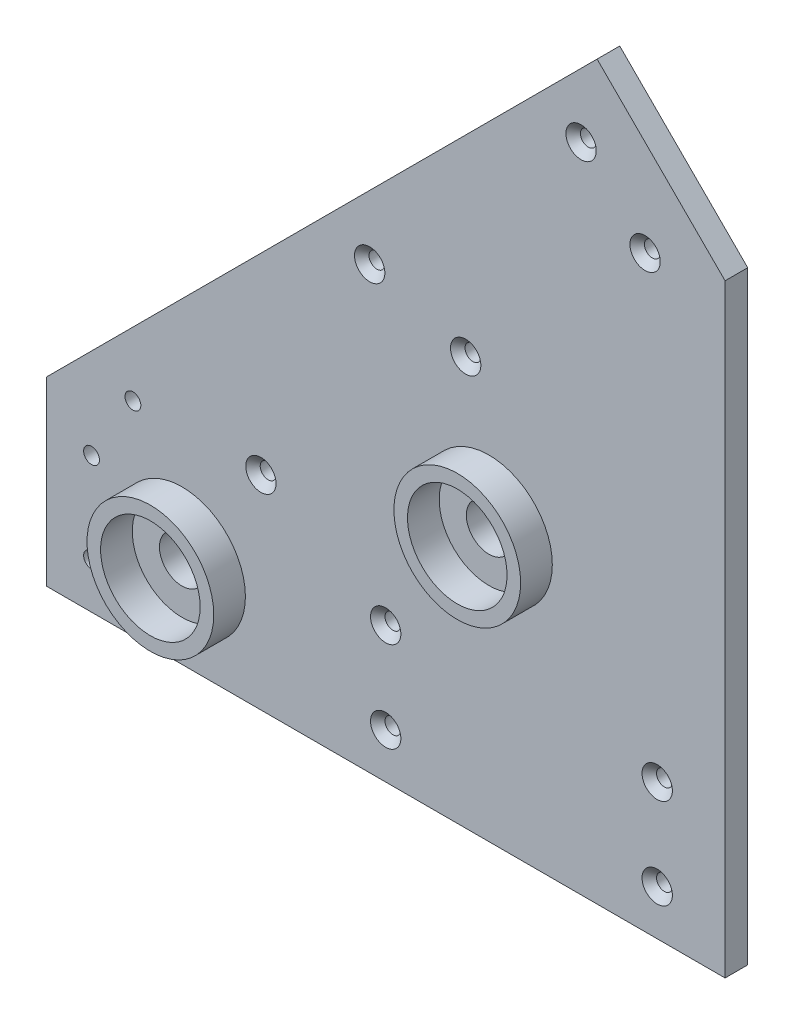
SolidWorks part; units mm, degrees
ref_plane "Front Plane" through (0, 0, 0) normal (0, 0, 1) x (1, 0, 0)
ref_plane "Top Plane" through (0, 0, 0) normal (0, 1, 0) x (1, 0, 0)
ref_plane "Right Plane" through (0, 0, 0) normal (1, 0, 0) x (0, 0, -1)
sketch "Sketch1" plane through (0, 0, 0) normal (0, 0, 1) x (1, 0, 0)
  line L0 (-75, 20) -> (46.7157, 141.7157)
  line L1 (-18.4315, 20) -> (75, 20) construction
  line L2 (-75, 20) -> (-75, -20)
  line L3 (-75, -20) -> (75, -20)
  line L4 (75, 20) -> (75, -20)
  line L5 (-75, 20) -> (75, -20) construction
  line L6 (-75, -20) -> (75, 20) construction
  line L7 (-75, -20) -> (75, -20)
  line L11 (46.7157, 141.7157) -> (75, 113.4315)
  line L12 (75, 113.4315) -> (-18.4315, 20) construction
  line L13 (-75, 0) -> (75, 0) construction
  line L14 (-75, 10) -> (75, 10) construction
  line L15 (-75, -10) -> (75, -10) construction
  line L16 (60.8579, 127.5736) -> (-46.7157, 20) construction
  line L17 (-75, 20) -> (-18.4315, 20) construction
  line L18 (53.7868, 134.6447) -> (-60.8579, 20) construction
  line L19 (67.9289, 120.5025) -> (-32.5736, 20) construction
  line L20 (75, 113.4315) -> (75, 20)
  line L21 (43.1802, 124.0381) -> (57.3223, 109.8959) construction
  line L22 (60, -10) -> (60, 10) construction
  line L23 (-65, -10) -> (-65, 10) construction
  circle A0 centre (-45, 0) radius 5
  circle A1 centre (22.8199, 40) radius 5
  circle A2 centre (-65, -10) radius 1.75
  circle A3 centre (0, 10) radius 1.75
  circle A4 centre (60, -10) radius 1.75
  circle A5 centre (-55.8579, 25) radius 1.75
  circle A6 centre (43.1802, 124.0381) radius 1.75
  circle A8 centre (-27.5736, 25) radius 1.75
  circle A9 centre (57.3223, 109.8959) radius 1.75
  circle A10 centre (22.8199, 40) radius 4 construction
  circle A11 centre (-3.5355, 77.3223) radius 1.75
  circle A12 centre (17.6777, 70.2513) radius 1.75
  circle A13 centre (60, 10) radius 1.75
  circle A14 centre (-65, 10) radius 1.75
  circle A15 centre (0, -10) radius 1.75
  point P0 (0, 0)
  dimension "D8" = 10
  dimension "D11" = 10
  dimension "D12" = 3.5
  dimension "D1" = 40
  dimension "D2" = 40
  dimension "D3" = 45
  dimension "D4" = 10
  dimension "D5" = 10
  dimension "D6" = 10
  dimension "D7" = 10
  dimension "D9" = 30
  dimension "D10" = 150
  dimension "D13" = 10
  dimension "D14" = 15
  dimension "D15" = 5
  dimension "D16" = 15
extrude "Boss-Extrude1" add sketch "Sketch1" along normal blind 5 contours L20 L11 L0 L2 L3 L4 A0 region at (14.2377, 41.2199, 0)
sketch "Sketch2" plane through (0, 0, 5) normal (0, 0, 1) x (1, 0, 0)
  circle A0 centre (-45, 0) radius 11
  circle A1 centre (-45, 0) radius 14
  circle A2 centre (22.8199, 40) radius 11
  circle A3 centre (22.8199, 40) radius 14
  dimension "D1" = 22
  dimension "D2" = 28
  dimension "D3" = 22
  dimension "D4" = 28
extrude "Boss-Extrude2" add sketch "Sketch2" along normal blind 7
chamfer "Chamfer1" distance 1.6 angle 45 9 edges at (-25.8236, 25, 5) (61.75, -10, 5) (61.75, 10, 5) (1.75, -10, 5) (1.75, 10, 5) (19.4277, 70.2513, 5) (-1.7855, 77.3223, 5) (59.0723, 109.8959, 5) (44.9302, 124.0381, 5)
